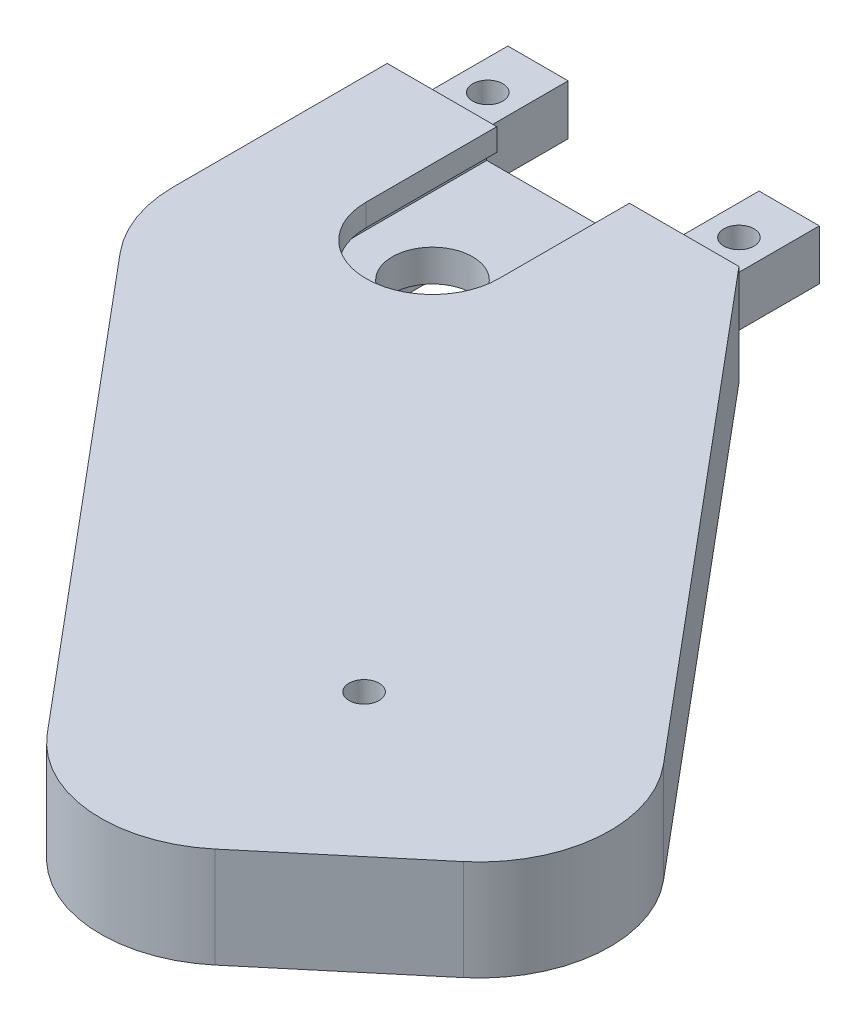
SolidWorks part; units mm, degrees
material "ABS"
ref_plane "Front Plane" through (0, 0, 0) normal (0, 0, 1) x (1, 0, 0)
ref_plane "Top Plane" through (0, 0, 0) normal (0, 1, 0) x (1, 0, 0)
ref_plane "Right Plane" through (0, 0, 0) normal (1, 0, 0) x (0, 0, -1)
sketch "Sketch1" plane through (0, 0, 0) normal (0, 1, 0) x (1, 0, 0)
  line L0 (0, 0) -> (6, 0)
  line L1 (6, 0) -> (6, -10)
  line L2 (6, -10) -> (25, -10)
  line L3 (25, -10) -> (25, 0)
  line L4 (25, 0) -> (31, 0)
  line L5 (31, 0) -> (31, -10)
  line L7 (0, -10) -> (0, 0)
  line L8 (0, -10) -> (-2, -10)
  line L11 (33, -36) -> (33, -10)
  line L12 (33, -10) -> (31, -10)
  line L13 (3, 0) -> (3, -5) construction
  line L14 (15.5, -10) -> (15.5, 0) construction
  line L15 (33, -36) -> (-2, -36)
  line L16 (-2, -36) -> (-2, -10)
  circle A0 centre (3, -5) radius 1.5
  circle A1 centre (28, -5) radius 1.5
  dimension "D9" = 3
  dimension "D1" = 36
  dimension "D2" = 35
  dimension "D3" = 10
  dimension "D4" = 6
  dimension "D5" = 2
  dimension "D6" = 6
  dimension "D7" = 2
  dimension "D8" = 5
sketch "Sketch10" plane through (0, 0, 0) normal (0, 1, 0) x (1, 0, 0)
  line L0 (-2, -36) -> (33, -36)
  line L1 (33, -36) -> (33, -10)
  line L2 (33, -10) -> (-2, -10)
  line L3 (-2, -36) -> (-2, -10)
extrude "Boss-Extrude4" add sketch "Sketch10" along normal blind 2.5
extrude "Boss-Extrude5" add sketch "Sketch1" against normal blind 5
sketch "Sketch11" plane through (0, -5, 0) normal (0, -1, 0) x (1, 0, 0)
  line L0 (-2, 36) -> (-2, 10)
  line L1 (-2, 10) -> (33, 10)
  line L2 (33, 10) -> (33, 36)
  line L3 (33, 36) -> (-2, 36)
extrude "Boss-Extrude6" add sketch "Sketch11" along normal blind 2.5
ref_plane "Plane1" through (0, -2.5, 0) normal (0, 1, 0) x (1, 0, 0)
sketch "Sketch3" plane through (0, 0, 10) normal (0, 0, -1) x (-1, 0, 0)
  line L0 (-22.1, 2.5) -> (-22.1, 0.2875)
  line L2 (-22.1, 0.2875) -> (-23.1, 0.2875)
  line L3 (-23.1, 0.2875) -> (-23.1, -0.9125)
  line L4 (-23.1, -0.9125) -> (-15.5, -0.9125)
  line L5 (-15.5, -0.9125) -> (-7.9, -0.9125)
  line L6 (-7.9, -0.9125) -> (-7.9, 0.2875)
  line L7 (-7.9, 0.2875) -> (-8.9, 0.2875)
  line L8 (-8.9, 0.2875) -> (-8.9, 2.5)
  line L9 (-8.9, 2.5) -> (-22.1, 2.5)
  line L10 (-25, -2.5) -> (-6, -2.5) construction
  line L13 (-15.5, -2.5) -> (-15.5, -0.9125) construction
  line L14 (-33, 2.5) -> (2, 2.5) construction
  line L15 (-6, -5) -> (-6, 0) construction
  line L16 (-25, -5) -> (-25, 0) construction
  dimension "D1" = 1.2
  dimension "D2" = 3.4125
  dimension "D3" = 13.2
  dimension "D4" = 15.2
extrude "Cut-Extrude1" cut sketch "Sketch3" against normal blind 13 and the other way through all
sketch "Sketch4" plane through (0, -0.9125, 0) normal (0, 1, 0) x (1, 0, 0)
  line L1 (23.1, -23) -> (7.9, -23) construction
  circle A0 centre (15.5, -23) radius 7.6
  dimension "D1" = 15.2
extrude "Cut-Extrude2" cut sketch "Sketch4" along normal up to surface (1.2 mm away) up to face at (8.4, 0.2875, 16.5)
sketch "Sketch5" plane through (0, -0.9125, 0) normal (0, 1, 0) x (1, 0, 0)
  line L1 (8.9, -23) -> (22.1, -23) construction
  circle A0 centre (15.5, -23) radius 6.6
  dimension "D1" = 13.2
extrude "Cut-Extrude3" cut sketch "Sketch5" along normal through all
sketch "Sketch12" plane through (0, -7.5, 0) normal (0, -1, 0) x (1, 0, 0)
  line L4 (33, 36) -> (-2, 36)
  line L5 (-2, 36) -> (-2, 10)
  line L6 (-2, 10) -> (33, 10)
  line L7 (33, 10) -> (33, 36)
  line L8 (33, 36) -> (-2, 36)
  line L9 (-2, 36) -> (-2, 10)
  line L10 (-2, 10) -> (33, 10)
  line L11 (33, 10) -> (33, 36)
  dimension "D1" = 0
sketch "Sketch8" plane through (0, -0.9125, 0) normal (0, 1, 0) x (1, 0, 0)
  circle A0 centre (15.5, -23) radius 4
  dimension "D1" = 8
extrude "Cut-Extrude6" cut sketch "Sketch8" against normal through all
ref_plane "Plane2" through (0, -2.5, 0) normal (0, 1, 0) x (1, 0, 0)
mirror "Mirror1" about plane through (0, -2.5, 0) normal (0, 1, 0) of "Cut-Extrude3", "Cut-Extrude2", "Cut-Extrude1"
sketch "Sketch13" plane through (0, 2.5, 0) normal (0, 1, 0) x (1, 0, 0)
  line L0 (15.5, -23) -> (73.3509, -91.944) construction
  line L1 (-2, -36) -> (70.6686, -122.603)
  line L2 (33, -10) -> (33, -36) construction
  line L3 (15.5, -23) -> (33, -23) construction
  line L9 (33, -23) -> (33, -10) construction
  line L10 (73.3509, -91.944) -> (87.3392, -108.6147) construction
  line L11 (15.5, -23) -> (15.5, -36) construction
  line L12 (15.5, -36) -> (-2, -36) construction
  line L13 (33, -10) -> (104.0099, -94.6263)
  line L14 (104.0099, -94.6263) -> (70.6686, -122.603)
  line L15 (73.3509, -91.944) -> (90.0216, -77.9556) construction
  line L16 (73.3509, -91.944) -> (56.6802, -105.9324) construction
  line L17 (-2, -36) -> (33, -36)
  line L18 (33, -36) -> (33, -10)
  line L19 (34.3343, -79.3015) -> (51.005, -65.3132) construction
  line L20 (51.005, -65.3132) -> (67.6756, -51.3248) construction
  circle A1 centre (51.005, -65.3132) radius 1.5
  circle A2 centre (28, -5) radius 1.5 construction
  dimension "D1" = 90
  dimension "D2" = 140
extrude "Boss-Extrude7" add sketch "Sketch13" against normal up to surface (10 mm away) up to face at (15.5, -7.5, 20.575)
fillet "Fillet1" radius 13 3 edges at (104.0099, -2.5, 94.6263) (70.6686, -2.5, 122.603) (-2, -2.5, 36)
ref_plane "Plane3" [suppressed] through (-2.2295, 0, 1.8708) normal (-0.766, 0, 0.6428) x (0.6428, 0, 0.766)
ref_plane "Plane4" [suppressed] through (0, -2.5, 0) normal (0, -1, 0) x (-1, 0, 0)
sketch "Sketch14" plane through (-18.9002, 0, 15.8591) normal (-0.766, 0, 0.6428) x (0.6428, 0, 0.766)
  line L0 (117.5822, 2.5) -> (124.1822, 2.5)
  line L1 (28.8724, 2.5) -> (139.3442, 2.5) construction
  line L2 (124.1822, 2.5) -> (124.1822, 0.1875)
  line L3 (124.1822, 0.1875) -> (125.1822, 0.1875)
  line L4 (125.1822, 0.1875) -> (125.1822, -0.9125)
  line L5 (125.1822, -0.9125) -> (117.5822, -0.9125)
  line L6 (117.5822, -0.9125) -> (109.9822, -0.9125)
  line L7 (109.9822, -0.9125) -> (109.9822, 0.1875)
  line L8 (109.9822, 0.1875) -> (110.9822, 0.1875)
  line L9 (110.9822, 0.1875) -> (110.9822, 2.5)
  line L10 (110.9822, 2.5) -> (117.5822, 2.5)
  dimension "D1" = 13.2
  dimension "D2" = 15.2
  dimension "D3" = 3.4125
  dimension "D4" = 1.1
extrude "Cut-Extrude7" [suppressed] cut sketch "Sketch14" against normal up to surface (21.762 mm away) up to plane "Plane3"
sketch "Sketch15" [suppressed] plane through (0, 0.1875, 0) normal (0, -1, 0) x (1, 0, 0)
  circle A0 centre (73.3509, 91.944) radius 7.6
  dimension "D1" = 15.2
extrude "Cut-Extrude8" [suppressed] cut sketch "Sketch15" along normal up to surface (1.1 mm away) up to face at (15.5, -0.9125, 27)
sketch "Sketch16" [suppressed] plane through (0, 0.1875, 0) normal (0, -1, 0) x (1, 0, 0)
  circle A0 centre (73.3509, 91.944) radius 6.6
  dimension "D1" = 13.2
extrude "Cut-Extrude9" [suppressed] cut sketch "Sketch16" against normal through all
mirror "Mirror2" [suppressed] about plane through (0, -2.5, 0) normal (0, -1, 0)
sketch "Sketch17" [suppressed] plane through (0, -0.9125, 0) normal (0, 1, 0) x (1, 0, 0)
  circle A0 centre (73.3509, -91.944) radius 4
  dimension "D1" = 8
extrude "Cut-Extrude10" [suppressed] cut sketch "Sketch17" against normal through all contours A0
sketch "Sketch18" plane through (0, 2.5, 0) normal (0, 1, 0) x (1, 0, 0)
  line L0 (47.19, -94.6224) -> (80.5314, -66.6457)
  line L1 (51.005, -65.3132) -> (63.8607, -80.634) construction
  line L8 (80.6271, -114.2468) -> (94.0513, -102.9826)
  line L9 (95.6537, -84.6677) -> (33, -10)
  line L10 (33, -10) -> (22.1, -10)
  line L11 (22.1, -10) -> (22.1, -23)
  line L12 (8.9, -23) -> (8.9, -10)
  line L13 (8.9, -10) -> (-2, -10)
  line L14 (-2, -10) -> (-2, -31.2684)
  line L15 (1.0414, -39.6246) -> (62.3123, -112.6444)
  line L16 (80.6271, -114.2468) -> (94.0513, -102.9826)
  line L17 (95.6537, -84.6677) -> (80.5314, -66.6457)
  line L23 (47.19, -94.6224) -> (62.3123, -112.6444)
  arc A4 (94.0513, -102.9826) -> (95.6537, -84.6677) centre (85.6951, -93.024) ccw
  arc A5 (8.9, -23) -> (22.1, -23) centre (15.5, -23) ccw
  arc A6 (-2, -31.2684) -> (1.0414, -39.6246) centre (11, -31.2684) ccw
  arc A7 (62.3123, -112.6444) -> (80.6271, -114.2468) centre (72.2709, -104.2882) ccw
  arc A8 (94.0513, -102.9826) -> (95.6537, -84.6677) centre (85.6951, -93.024) ccw
  arc A11 (62.3123, -112.6444) -> (80.6271, -114.2468) centre (72.2709, -104.2882) ccw
  dimension "D2" = 20
  dimension "D1" = 0
extrude "Cut-Extrude11" cut sketch "Sketch18" against normal through all
fillet "Fillet2" radius 13 2 edges at (80.5314, -2.5, 66.6457) (47.19, -2.5, 94.6224)
